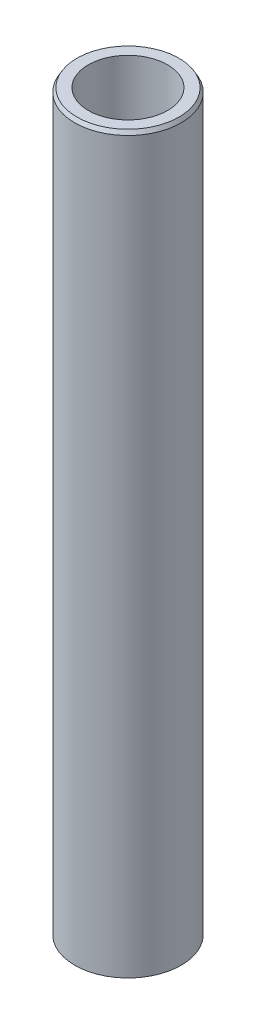
SolidWorks part; units mm, degrees
ref_plane "Front Plane" through (0, 0, 0) normal (0, 0, 1) x (1, 0, 0)
ref_plane "Top Plane" through (0, 0, 0) normal (0, 1, 0) x (1, 0, 0)
ref_plane "Right Plane" through (0, 0, 0) normal (1, 0, 0) x (0, 0, -1)
sketch "Sketch1" plane through (0, 0, 0) normal (0, 1, 0) x (1, 0, 0)
  circle A0 centre (0, 0) radius 37.5
  dimension "SHAFT_OD" = 75
extrude "Boss-Extrude1" add sketch "Sketch1" along normal blind 518.3207
sketch "Sketch2" plane through (0, 0, 0) normal (0, 1, 0) x (1, 0, 0)
  circle A0 centre (0, 0) radius 27.9242
  dimension "BORE_D" = 55.8484
extrude "Cut-Extrude1" cut sketch "Sketch2" along normal through all
chamfer "Chamfer1" distance 2.7178 angle 30 2 edges at (0, 518.3207, 37.5) (0, 0, 37.5) first distance on face at (0, 518.3207, 37.5) first distance on face at (0, 0, 27.9242)
